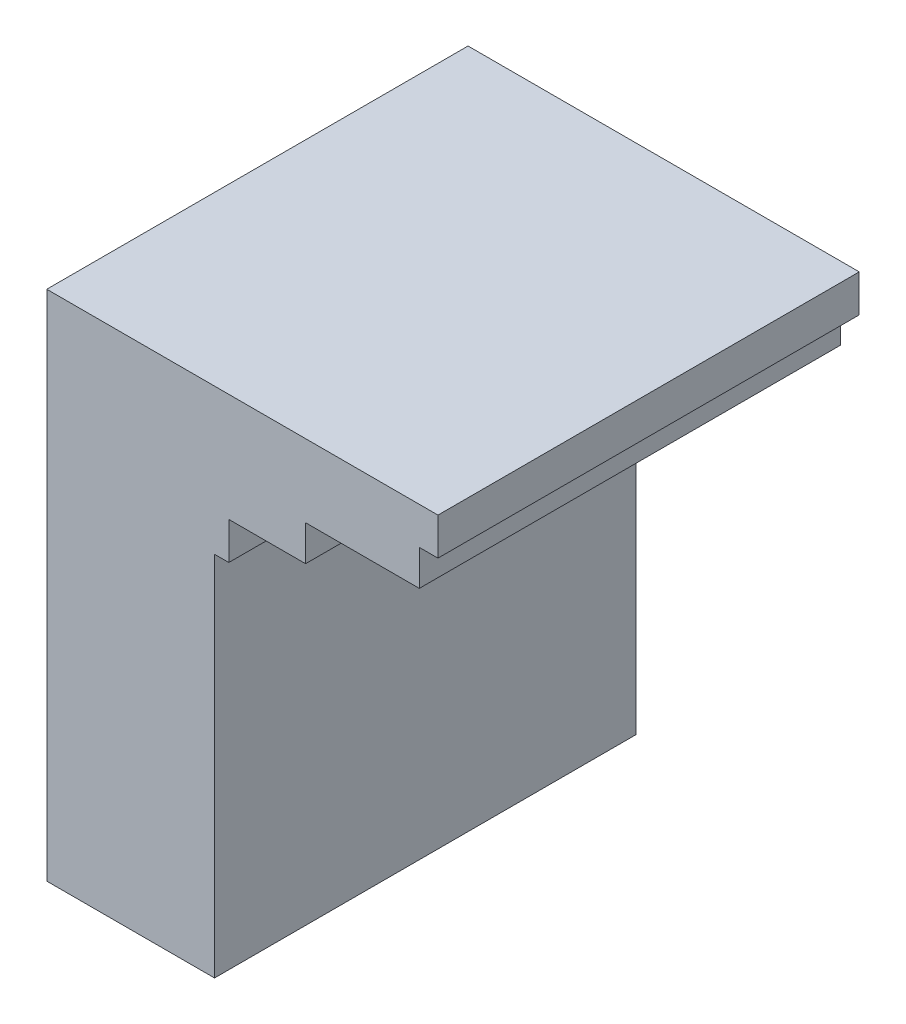
SolidWorks part; units mm, degrees
ref_plane "Front Plane" through (0, 0, 0) normal (0, 0, 1) x (1, 0, 0)
ref_plane "Top Plane" through (0, 0, 0) normal (0, 1, 0) x (1, 0, 0)
ref_plane "Right Plane" through (0, 0, 0) normal (1, 0, 0) x (0, 0, -1)
sketch "Sketch1" plane through (0, 0, 0) normal (0, 0, 1) x (1, 0, 0)
  line L0 (-300, 25) -> (300, 25) construction
  line L1 (-300, -250) -> (-300, 250) construction
  line L2 (300, -250) -> (-300, -250) construction
  line L3 (-210, -250) -> (-210, -53.1315) construction
  line L4 (-210, -53.1315) -> (-190.95, -53.1315) construction
  line L8 (-161.15, -14.05) -> (161.15, -14.05) construction
  line L9 (-100.1317, -14.05) -> (-100.1317, 5) construction
  line L10 (-100.1317, 5) -> (100.1317, 5) construction
  line L11 (-300, 25) -> (-90.1317, 25)
  line L12 (-300, -250) -> (-300, 25)
  line L13 (-210, -250) -> (-300, -250)
  line L14 (-210, -250) -> (-210, -53.1315)
  line L15 (-210, -53.1315) -> (-204.3373, -53.1315)
  line L16 (-161.15, -14.05) -> (161.15, -14.05) construction
  line L18 (-161.15, -33.1) -> (-161.15, -14.05) construction
  line L19 (-161.15, -14.05) -> (-100.1317, -14.05)
  line L20 (-100.1317, -14.05) -> (-100.1317, 5)
  line L21 (-100.1317, 5) -> (-90.1317, 5)
  line L22 (-100.1317, 5) -> (-90.1317, 5)
  line L23 (-90.1317, 5) -> (-90.1317, 25)
  line L24 (202.3375, -33.1) -> (-202.3373, -33.1) construction
  line L25 (-202.3373, -53.1315) -> (-202.3373, -33.1) construction
  line L26 (-161.15, -14.05) -> (-100.1317, -14.05)
  line L27 (-161.15, -33.1) -> (-161.15, -14.05)
  line L28 (-161.15, -33.1) -> (-202.3373, -33.1)
  line L29 (-202.3373, -53.1315) -> (-202.3373, -33.1)
  line L30 (-204.3373, -53.1315) -> (-202.3373, -53.1315)
extrude "Boss-Extrude1" add sketch "Sketch1" along normal up to surface (226 mm away) contours L21 L23 L11 L12 L13 L14 L15 L19 L20 region at (-237.4291, -91.8876, 0)
